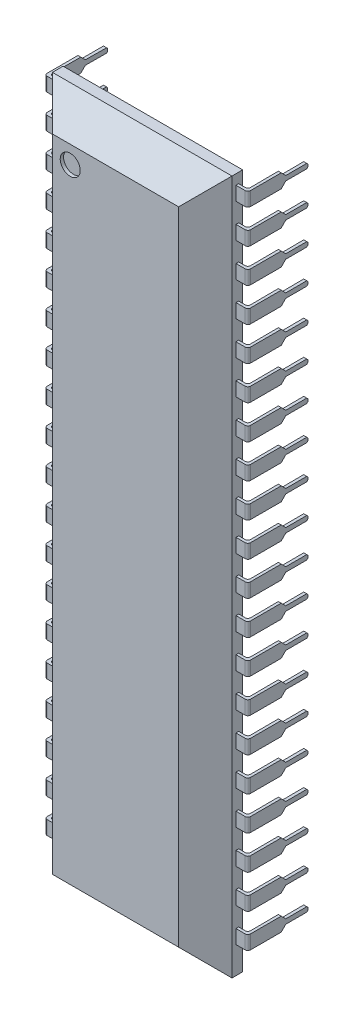
SolidWorks part; units mm, degrees
ref_plane "前视基准面" through (0, 0, 0) normal (0, 0, 1) x (1, 0, 0)
ref_plane "上视基准面" through (0, 0, 0) normal (0, 1, 0) x (1, 0, 0)
ref_plane "右视基准面" through (0, 0, 0) normal (1, 0, 0) x (0, 0, -1)
sketch "草图1" plane through (0, 0, 0) normal (0, 0, 1) x (1, 0, 0)
  line L0 (0, 0) -> (19.0687, 0) construction
  line L1 (0, 0) -> (0, 13.6921) construction
  line L2 (6.731, 26.035) -> (-6.731, 26.035)
  line L3 (6.731, 26.035) -> (6.731, -26.035)
  line L4 (-6.731, 26.035) -> (-6.731, -26.035)
  line L5 (6.731, -26.035) -> (-6.731, -26.035)
  point P5 (-6.731, 0)
  point P9 (0, 26.035)
  point P11 (6.731, 0)
  dimension "D1" = 52.07
  dimension "D2" = 13.462
extrude "凸台-拉伸1" add sketch "草图1" along normal blind 4.8
ref_plane "基准面1" through (0, 0, 2.4) normal (0, 0, 1) x (1, 0, 0)
chamfer "倒角1" distance 2 angle 45 8 edges at (6.731, 0, 0) (0, 26.035, 0) (-6.731, 0, 0) (0, -26.035, 0) (0, 26.035, 4.8) (-6.731, 0, 4.8) (0, -26.035, 4.8) (6.731, 0, 4.8)
sketch "草图2" plane through (0, 0, 4.8) normal (0, 0, 1) x (1, 0, 0)
  line L0 (-4.731, 24.035) -> (2.2213, 17.0827) construction
  line L1 (4.731, 24.035) -> (-4.731, 24.035) construction
  circle A0 centre (-3.3963, 22.7003) radius 0.75
  dimension "D2" = 1.5
  dimension "D1" = 45
extrude "标记" cut sketch "草图2" against normal blind 0.25
ref_plane "基准面2" through (0, -23.495, 0) normal (0, -1, 0) x (1, 0, 0)
sketch "草图3" plane through (0, -23.495, 0) normal (0, -1, 0) x (1, 0, 0)
  line L0 (6.731, 2.4) -> (7.6477, 2.4) construction
  line L1 (6.731, 2.9286) -> (6.731, 1.8406) construction
  line L2 (0, 5.0608) -> (0, -4.1502) construction
  line L3 (7.62, 2.3015) -> (7.62, 2.2985)
  line L4 (6.731, 2.5015) -> (7.42, 2.5015)
  line L5 (6.731, 2.8) -> (6.731, 2) construction
  line L6 (6.731, 2.2985) -> (7.217, 2.2985)
  line L7 (6.731, 2.5015) -> (6.731, 2.2985)
  line L8 (7.417, 2.0985) -> (7.417, 1.8563)
  line L9 (7.62, -2) -> (7.391, -2)
  line L10 (4.731, 0) -> (-4.731, 0) construction
  line L11 (7.417, 1.8563) -> (7.391, -2)
  line L12 (7.62, 2.3015) -> (7.62, -2)
  arc A0 (7.217, 2.2985) -> (7.417, 2.0985) centre (7.217, 2.0985) cw
  arc A1 (7.62, 2.3015) -> (7.42, 2.5015) centre (7.42, 2.3015) ccw
  point P12 (7.62, 2.4)
  point P20 (7.62, 2.5015)
  dimension "D4" = 0.2
  dimension "D1" = 0.203
  dimension "D2" = 15.24
  dimension "D3" = 0.203
  dimension "D5" = 2
extrude "引脚4" add sketch "草图3" along normal mid plane 1.041 contours L3 A1 L4 L7 L6 A0 L8 L11 L9 L12 region at (7.4558, -23.495, 0.4766)
sketch "草图4" plane through (7.62, 0, 0) normal (1, 0, 0) x (0, 0, -1)
  line L0 (3.575, -23.495) -> (-3.7143, -23.495) construction
  line L1 (-3.8703, -23.495) -> (3.8703, -23.495) construction
  line L2 (0, -22.9745) -> (0.3425, -23.317)
  line L5 (0, 24.035) -> (0, -24.035) construction
  line L6 (-2.3015, -22.9745) -> (2, -22.9745) construction
  line L7 (1.9155, -23.317) -> (0.3425, -23.317)
  line L8 (2, -23.317) -> (2, -22.9745)
  line L9 (2, -24.0155) -> (2, -22.9745) construction
  line L10 (2, -22.9745) -> (0, -22.9745)
  line L11 (1.9155, -23.673) -> (0.3425, -23.673)
  line L12 (2, -23.673) -> (2, -24.0155)
  line L13 (2, -24.0155) -> (0, -24.0155)
  line L14 (0, -24.0155) -> (0.3425, -23.673)
  line L15 (2, -23.4015) -> (1.9155, -23.317)
  line L16 (2, -23.317) -> (2, -23.4015)
  line L17 (2, -23.673) -> (2, -23.5885)
  line L18 (2, -23.5885) -> (1.9155, -23.673)
  dimension "D1" = 0.356
  dimension "D2" = 135
  dimension "D3" = 45
extrude "引脚2" cut sketch "草图4" against normal up to next
pattern_linear "引脚1" count 20 spacing 2.54 along (0, 1, 0) of "引脚2", "引脚4"
mirror "引脚3" about plane through (0, 0, 0) normal (1, 0, 0) of "引脚4", "引脚2", "引脚1"
